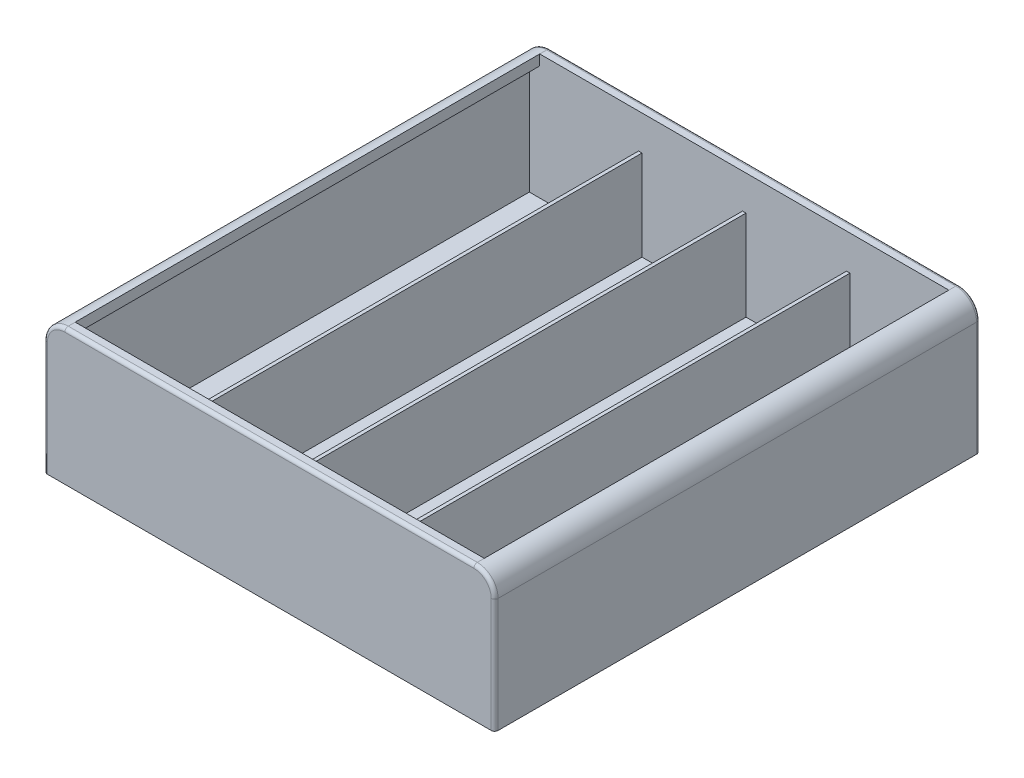
SolidWorks part; units mm, degrees
material "PP Copolymer"
ref_plane "Front" through (0, 0, 0) normal (0, 0, 1) x (1, 0, 0)
ref_plane "Top" through (0, 0, 0) normal (0, 1, 0) x (1, 0, 0)
ref_plane "Right" through (0, 0, 0) normal (1, 0, 0) x (0, 0, -1)
sketch "Sketch1" plane through (0, 0, 0) normal (0, 1, 0) x (1, 0, 0)
  line L1 (32.5, 35) -> (-32.5, 35)
  line L2 (32.5, 35) -> (32.5, -35)
  line L3 (32.5, -35) -> (-32.5, -35)
  line L4 (-32.5, 35) -> (-32.5, -35)
  line L5 (32.5, 35) -> (-32.5, -35) construction
  line L6 (32.5, -35) -> (-32.5, 35) construction
  point P0 (0, 0)
  dimension "D1" = 65
  dimension "D2" = 70
extrude "Boss-Extrude1" add sketch "Sketch1" along normal blind 19.5
fillet "Fillet1" radius 3 2 edges at (32.5, 19.5, 0) (-32.5, 19.5, 0)
fillet "Fillet2" radius 0.5 10 edges at (-32.5, 8.25, 35) (-31.6213, 18.6213, 35) (32.5, 8.25, 35) (31.6213, 18.6213, 35) (32.5, 8.25, -35) (31.6213, 18.6213, -35) (-32.5, 8.25, -35) (-31.6213, 18.6213, -35) (0, 19.5, 35) (0, 19.5, -35)
shell "Shell1" thickness 1.5 removed face at (0, 19.5, 0)
sketch "Sketch2" plane through (0, 1.5, 0) normal (0, 1, 0) x (1, 0, 0)
  line L0 (0, -33.5) -> (0, 33.5)
  line L1 (31, 33.5) -> (-31, 33.5) construction
  point P6 (0, 0)
extrude "Extrude-Thin1" add sketch "Sketch2" along normal offset from surface (13 mm away) 5 thin up to face at (0, 19.5, 34) thin type mid plane wall 0.5
pattern_linear "LPattern1" count 2 spacing 15 along (-1, 0, 0) count 2 spacing 15 along (1, 0, 0) of "Extrude-Thin1" pattern seed only yes
mirror "Mirror2" [suppressed] about plane through (0, 0, 0) normal (0, 1, 0) of bodies 103
